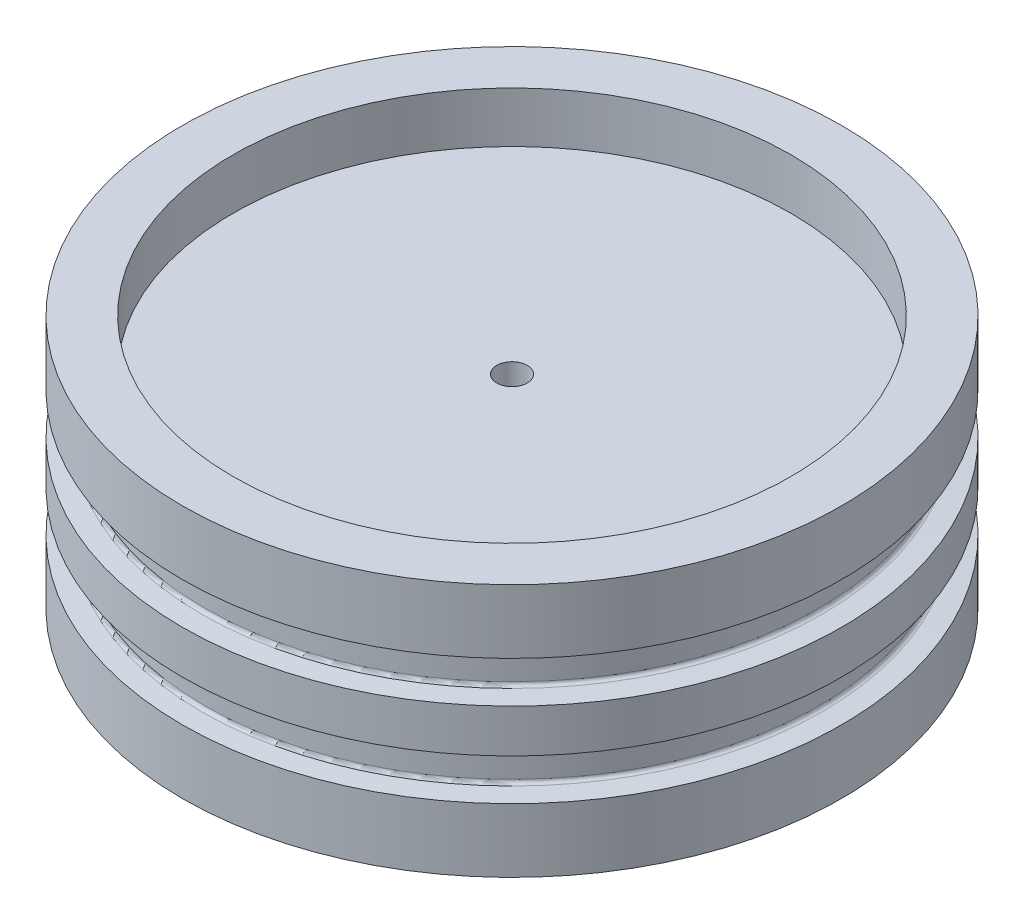
SolidWorks part; units mm, degrees
material "1060 Alloy"
ref_plane "Front Plane" through (0, 0, 0) normal (0, 0, 1) x (1, 0, 0)
ref_plane "Top Plane" through (0, 0, 0) normal (0, 1, 0) x (1, 0, 0)
ref_plane "Right Plane" through (0, 0, 0) normal (1, 0, 0) x (0, 0, -1)
sketch "Sketch1" plane through (0, 0, 0) normal (0, 0, 1) x (1, 0, 0)
  line L0 (0, 0) -> (0, 25.4) construction
  line L1 (-41.275, 12.7) -> (-41.275, 44.45)
  line L2 (-41.275, 12.7) -> (-6.35, 12.7)
  line L3 (-1.9133, 0) -> (-1.9133, 38.1)
  line L4 (-1.9133, 38.1) -> (-34.925, 38.1)
  line L5 (-34.925, 38.1) -> (-34.925, 44.45)
  line L6 (-34.925, 44.45) -> (-41.275, 44.45)
  line L8 (-1.9133, 0) -> (-6.35, 0)
  line L9 (-6.35, 0) -> (-6.35, 12.7)
  line L11 (55, 0) -> (-55, 0) construction
  dimension "D1" = 1.9133
  dimension "D2" = 34.925
  dimension "D3" = 31.75
  dimension "D4" = 6.35
  dimension "D5" = 25.4
  dimension "D6" = 12.7
  dimension "D7" = 6.35
revolve "Revolve1" add sketch "Sketch1" angle 360 about L0
ref_plane "Plane1" through (0, 0, 0) normal (-1, 0, 0) x (0, 0, -1)
ref_plane "Plane2" through (0, 0, 0) normal (-1, 0, 0) x (0, 0, -1)
ref_plane "Plane3" through (0, 0, 0) normal (-1, 0, 0) x (0, 0, -1)
ref_plane "Plane4" through (0, 0, 0) normal (-1, 0, 0) x (0, 0, -1)
ref_plane "Plane5" through (0, 0, 0) normal (-1, 0, 0) x (0, 0, -1)
ref_plane "Plane6" through (0, 0, 0) normal (-1, 0, 0) x (0, 0, -1)
ref_plane "Plane7" through (0, 0, 0) normal (-1, 0, 0) x (0, 0, -1)
sketch "Sketch15" plane through (0, 0, 0) normal (-1, 0, 0) x (0, 0, -1)
  line L0 (38.8614, -31.4918) -> (41.3639, -31.2728)
  line L1 (41.3639, -31.2728) -> (41.3639, -36.4605)
  line L2 (41.3639, -36.4605) -> (38.8614, -36.2416)
  line L3 (38.4556, -35.7988) -> (38.4556, -31.9346)
  line L4 (0, 50) -> (0, -50) construction
  line L5 (-41.275, -44.45) -> (41.275, -44.45) construction
  arc A0 (38.8614, -36.2416) -> (38.4556, -35.7988) centre (38.9001, -35.7988) cw
  arc A1 (38.4556, -31.9346) -> (38.8614, -31.4918) centre (38.9001, -31.9346) cw
  point P11 (38.4556, -33.8667)
  dimension "D1" = 10.5833
revolve "Groove for AS 568-234, O-Ring1" cut sketch "Sketch15"
pattern_linear "LPattern2" count 2 spacing 10.5833 along (0, -1, 0) of "Groove for AS 568-234, O-Ring1"
